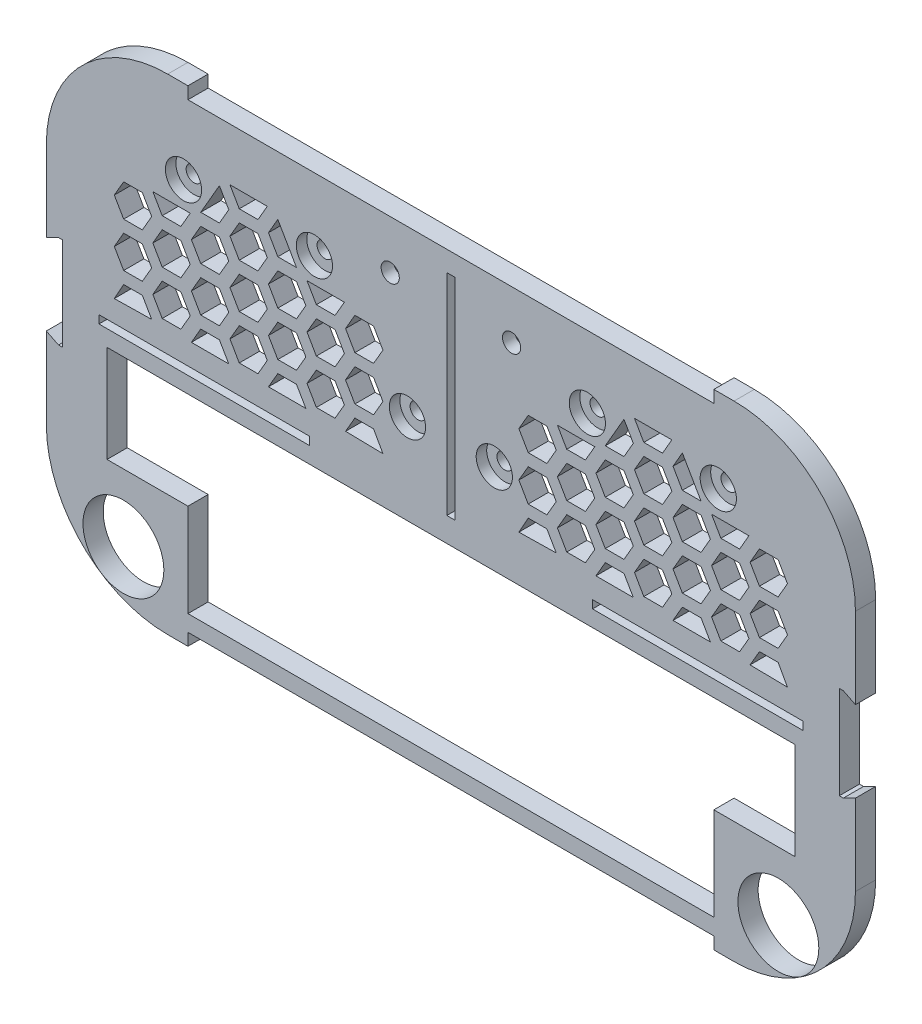
SolidWorks part; units mm, degrees
ref_plane "前视基准面" through (0, 0, 0) normal (0, 0, 1) x (1, 0, 0)
ref_plane "上视基准面" through (0, 0, 0) normal (0, 1, 0) x (1, 0, 0)
ref_plane "右视基准面" through (0, 0, 0) normal (1, 0, 0) x (0, 0, -1)
sketch "草图1" plane through (0, 0, 0) normal (0, 0, 1) x (1, 0, 0)
  line L1 (70, 60) -> (-70, 60)
  line L2 (-100, 30) -> (-100, -30)
  line L4 (70, -60) -> (-70, -60)
  line L5 (100, 30) -> (100, -30)
  arc A0 (-70, 60) -> (-100, 30) centre (-70, 30) ccw
  arc A1 (-70, -60) -> (-100, -30) centre (-70, -30) cw
  arc A2 (70, -60) -> (100, -30) centre (70, -30) ccw
  arc A3 (70, 60) -> (100, 30) centre (70, 30) cw
  point P12 (0, -60)
extrude "凸台-拉伸1" add sketch "草图1" along normal blind 5
sketch "草图2" plane through (0, 0, 0) normal (0, 0, 1) x (1, 0, 0)
  circle A0 centre (-80.95, 46.6721) radius 10
  circle A1 centre (80.95, 46.6721) radius 10
  circle A2 centre (80.95, -46.6721) radius 10
  circle A3 centre (-80.95, -46.6721) radius 10
  point P3 (0, 0)
  point P4 (0, 0)
extrude "孔" cut sketch "草图2" along normal blind 4 contours A1 | A0 region at (-80.95, 46.6721, 0) region at (80.95, 46.6721, 0)
extrude "穿孔" cut sketch "草图2<3>" along normal up to next contours A2 | A3 region at (80.95, -46.6721, 0) region at (-80.95, -46.6721, 0)
sketch "草图2<3>" plane through (0, 0, 0) normal (0, 0, 1) x (1, 0, 0) same geometry as "草图2"
sketch "草图3" plane through (0, 0, 0) normal (0, 0, 1) x (1, 0, 0)
  line L8 (-85, -6) -> (-85, -30)
  line L12 (-70, -30) -> (-65, -30)
  line L22 (-85, -30) -> (-70, -30)
  line L26 (85, -30) -> (70, -30)
  line L32 (70, -30) -> (65, -30)
  line L37 (-65, -30) -> (-65, -53)
  line L39 (65, -53) -> (65, -30)
  line L40 (-65, -60) -> (-65, -57)
  line L41 (-70, -60) -> (70, -60) construction
  line L42 (-65, -57) -> (65, -57)
  line L43 (65, -57) -> (65, -60)
  line L44 (-65, -60) -> (65, -60)
  line L50 (-100, -10) -> (-97, -11.5)
  line L53 (-100, 10) -> (-100, -10)
  line L55 (-85, -6) -> (85, -6)
  line L56 (85, -6) -> (85, -30)
  line L88 (65, -53) -> (-65, -53)
  line L89 (87, 0) -> (87, -2)
  line L90 (87, -2) -> (35, -2)
  line L92 (87, 0) -> (37, 0)
  line L96 (35, 0) -> (35, -2)
  line L105 (-35, 0) -> (-35, -2)
  line L109 (-87, 0) -> (-37, 0)
  line L110 (-87, -2) -> (-35, -2)
  line L111 (-87, 0) -> (-87, -2)
  line L112 (97, 11.5) -> (96, 11.5)
  line L114 (-97, 11.5) -> (-100, 10)
  line L115 (97, 11.5) -> (100, 10)
  line L118 (100, 10) -> (100, -10)
  line L119 (100, -10) -> (97, -11.5)
  line L120 (96, 11.5) -> (96, -11.5)
  line L121 (96, -11.5) -> (97, -11.5)
  line L122 (-97, 11.5) -> (-96, 11.5)
  line L123 (-96, 11.5) -> (-96, -11.5)
  line L124 (-96, -11.5) -> (-97, -11.5)
  line L125 (0, 0) -> (-1, 0)
  line L126 (-1, 0) -> (-1, 50)
  line L128 (1, 50) -> (1, 0)
  line L129 (1, 0) -> (0, 0)
  line L130 (-1, 50) -> (-1, 52)
  line L131 (-1, 52) -> (1, 52)
  line L132 (1, 52) -> (1, 50)
  line L133 (-37, 0) -> (-35, 0)
  line L134 (35, 0) -> (37, 0)
  line L135 (-65, 57) -> (-65, 60)
  line L136 (-65, 57) -> (65, 57)
  line L138 (65, 57) -> (65, 60)
  line L139 (65, 60) -> (-65, 60)
extrude "切除-拉伸4" cut sketch "草图3" along normal up to next
hole_wizard "M3.5 六角头机械螺钉的柱形沉头孔1" positions "3D草图1" profile "草图4" counterbore size "M3.5" standard "ANSI Metric" end condition through all
sketch3d "3D草图1"
  point P31 (-66.0951, 39.3344, 5)
  point P33 (-33.736, 39.2649, 5)
  point P35 (-10.7334, 16.264, 5)
  point P78 (33.736, 39.2649, 5)
  point P80 (10.7334, 16.264, 5)
  point P82 (66.0951, 39.3344, 5)
sketch "草图4" plane through (-66.0951, 39.3344, 5) normal (1, 0, 0) x (0, -1, 0)
  line L0 (0, 0) -> (0, 5)
  line L1 (0, 5) -> (1.95, 5)
  line L3 (1.95, 5) -> (1.95, 2.6)
  line L4 (1.95, 2.6) -> (4.48, 2.6)
  line L5 (4.48, 2.6) -> (4.48, 0)
  line L7 (4.48, 0) -> (0, 0)
  line L11 (0, -6.35) -> (0, 107.95) construction
  dimension "通孔孔直径" = 3.9
  dimension "通孔孔深度" = 5
  dimension "柱形沉头孔直径" = 8.96
  dimension "柱形沉头孔深度" = 2.6
sketch "草图5" plane through (0, 0, 0) normal (0, 0, 1) x (1, 0, 0)
  line L4 (-35.8549, 5.5) -> (-38.1643, 9.5)
  line L6 (-38.1643, 9.5) -> (-42.7831, 9.5)
  line L13 (-42.7831, 9.5) -> (-45.0925, 5.5)
  line L17 (-26.3286, 11) -> (-28.638, 15)
  line L18 (-28.638, 15) -> (-33.2568, 15)
  line L19 (-33.2568, 15) -> (-35.5662, 11)
  line L20 (-35.5662, 11) -> (-33.2568, 7)
  line L21 (-33.2568, 7) -> (-28.638, 7)
  line L22 (-28.638, 7) -> (-26.3286, 11)
  line L23 (-16.8024, 16.5) -> (-19.1118, 20.5)
  line L24 (-19.1118, 20.5) -> (-23.7306, 20.5)
  line L25 (-23.7306, 20.5) -> (-26.04, 16.5)
  line L26 (-26.04, 16.5) -> (-23.7306, 12.5)
  line L27 (-23.7306, 12.5) -> (-19.1118, 12.5)
  line L28 (-19.1118, 12.5) -> (-16.8024, 16.5)
  line L29 (-35.8549, 16.5) -> (-38.1643, 20.5)
  line L30 (-38.1643, 20.5) -> (-42.7831, 20.5)
  line L31 (-42.7831, 20.5) -> (-45.0925, 16.5)
  line L32 (-45.0925, 16.5) -> (-42.7831, 12.5)
  line L33 (-42.7831, 12.5) -> (-38.1643, 12.5)
  line L34 (-38.1643, 12.5) -> (-35.8549, 16.5)
  line L35 (-26.3286, 22) -> (-28.638, 26)
  line L36 (-28.638, 26) -> (-33.2568, 26)
  line L37 (-33.2568, 26) -> (-35.5662, 22)
  line L38 (-35.5662, 22) -> (-33.2568, 18)
  line L39 (-33.2568, 18) -> (-28.638, 18)
  line L40 (-28.638, 18) -> (-26.3286, 22)
  line L41 (-16.8024, 27.5) -> (-19.1118, 31.5)
  line L42 (-19.1118, 31.5) -> (-23.7306, 31.5)
  line L43 (-23.7306, 31.5) -> (-26.04, 27.5)
  line L44 (-26.04, 27.5) -> (-23.7306, 23.5)
  line L45 (-23.7306, 23.5) -> (-19.1118, 23.5)
  line L46 (-19.1118, 23.5) -> (-16.8024, 27.5)
  line L47 (-35.8549, 27.5) -> (-38.1643, 31.5)
  line L48 (-38.1643, 31.5) -> (-42.7831, 31.5)
  line L49 (-42.7831, 31.5) -> (-45.0925, 27.5)
  line L50 (-45.0925, 27.5) -> (-42.7831, 23.5)
  line L51 (-42.7831, 23.5) -> (-38.1643, 23.5)
  line L52 (-38.1643, 23.5) -> (-35.8549, 27.5)
  line L56 (-35.5662, 33) -> (-33.2568, 29)
  line L57 (-33.2568, 29) -> (-28.638, 29)
  line L58 (-28.638, 29) -> (-26.3286, 33)
  line L67 (-42.7831, 42.5) -> (-45.0925, 38.5)
  line L68 (-45.0925, 38.5) -> (-42.7831, 34.5)
  line L69 (-42.7831, 34.5) -> (-38.1643, 34.5)
  line L83 (-45.3812, 11) -> (-47.6906, 15)
  line L84 (-47.6906, 15) -> (-52.3094, 15)
  line L85 (-52.3094, 15) -> (-54.6188, 11)
  line L86 (-54.6188, 11) -> (-52.3094, 7)
  line L87 (-52.3094, 7) -> (-47.6906, 7)
  line L88 (-47.6906, 7) -> (-45.3812, 11)
  line L89 (-45.3812, 22) -> (-47.6906, 26)
  line L90 (-47.6906, 26) -> (-52.3094, 26)
  line L91 (-52.3094, 26) -> (-54.6188, 22)
  line L92 (-54.6188, 22) -> (-52.3094, 18)
  line L93 (-52.3094, 18) -> (-47.6906, 18)
  line L94 (-47.6906, 18) -> (-45.3812, 22)
  line L95 (-45.3812, 33) -> (-47.6906, 37)
  line L96 (-47.6906, 37) -> (-52.3094, 37)
  line L97 (-52.3094, 37) -> (-54.6188, 33)
  line L98 (-54.6188, 33) -> (-52.3094, 29)
  line L99 (-52.3094, 29) -> (-47.6906, 29)
  line L100 (-47.6906, 29) -> (-45.3812, 33)
  line L125 (-42.7831, 42.5) -> (-38.1643, 34.5)
  line L126 (-35.5662, 33) -> (-26.3286, 33)
  line L127 (-45.0925, 5.5) -> (-35.8549, 5.5)
  line L129 (-54.9075, 5.5) -> (-64.1451, 5.5)
  line L130 (-64.4338, 33) -> (-73.6714, 33)
  line L131 (-57.2169, 42.5) -> (-61.8357, 34.5)
  line L132 (-57.2169, 34.5) -> (-61.8357, 34.5)
  line L133 (-54.9075, 38.5) -> (-57.2169, 34.5)
  line L134 (-57.2169, 42.5) -> (-54.9075, 38.5)
  line L135 (-71.362, 29) -> (-73.6714, 33)
  line L136 (-66.7432, 29) -> (-71.362, 29)
  line L137 (-64.4338, 33) -> (-66.7432, 29)
  line L138 (-61.8357, 23.5) -> (-64.1451, 27.5)
  line L139 (-57.2169, 23.5) -> (-61.8357, 23.5)
  line L140 (-54.9075, 27.5) -> (-57.2169, 23.5)
  line L141 (-57.2169, 31.5) -> (-54.9075, 27.5)
  line L142 (-61.8357, 31.5) -> (-57.2169, 31.5)
  line L143 (-64.1451, 27.5) -> (-61.8357, 31.5)
  line L144 (-80.8882, 23.5) -> (-83.1976, 27.5)
  line L145 (-76.2694, 23.5) -> (-80.8882, 23.5)
  line L146 (-73.96, 27.5) -> (-76.2694, 23.5)
  line L147 (-76.2694, 31.5) -> (-73.96, 27.5)
  line L148 (-80.8882, 31.5) -> (-76.2694, 31.5)
  line L149 (-83.1976, 27.5) -> (-80.8882, 31.5)
  line L150 (-71.362, 18) -> (-73.6714, 22)
  line L151 (-66.7432, 18) -> (-71.362, 18)
  line L152 (-64.4338, 22) -> (-66.7432, 18)
  line L153 (-66.7432, 26) -> (-64.4338, 22)
  line L154 (-71.362, 26) -> (-66.7432, 26)
  line L155 (-73.6714, 22) -> (-71.362, 26)
  line L156 (-61.8357, 12.5) -> (-64.1451, 16.5)
  line L157 (-57.2169, 12.5) -> (-61.8357, 12.5)
  line L158 (-54.9075, 16.5) -> (-57.2169, 12.5)
  line L159 (-57.2169, 20.5) -> (-54.9075, 16.5)
  line L160 (-61.8357, 20.5) -> (-57.2169, 20.5)
  line L161 (-64.1451, 16.5) -> (-61.8357, 20.5)
  line L162 (-80.8882, 12.5) -> (-83.1976, 16.5)
  line L163 (-76.2694, 12.5) -> (-80.8882, 12.5)
  line L164 (-73.96, 16.5) -> (-76.2694, 12.5)
  line L165 (-76.2694, 20.5) -> (-73.96, 16.5)
  line L166 (-80.8882, 20.5) -> (-76.2694, 20.5)
  line L167 (-83.1976, 16.5) -> (-80.8882, 20.5)
  line L168 (-71.362, 7) -> (-73.6714, 11)
  line L169 (-66.7432, 7) -> (-71.362, 7)
  line L170 (-64.4338, 11) -> (-66.7432, 7)
  line L171 (-66.7432, 15) -> (-64.4338, 11)
  line L172 (-71.362, 15) -> (-66.7432, 15)
  line L173 (-73.6714, 11) -> (-71.362, 15)
  line L174 (-57.2169, 9.5) -> (-54.9075, 5.5)
  line L175 (-61.8357, 9.5) -> (-57.2169, 9.5)
  line L176 (-64.1451, 5.5) -> (-61.8357, 9.5)
  line L181 (-52.3094, 40) -> (-47.6906, 40)
  line L184 (-52.3094, 44) -> (-54.6188, 44)
  line L185 (-54.6188, 44) -> (-52.3094, 40)
  line L186 (-52.3094, 44) -> (-45.3812, 44)
  line L187 (-45.3812, 44) -> (-47.6906, 40)
  line L188 (-21.4212, 9.5) -> (-23.7306, 9.5)
  line L191 (-26.04, 5.5) -> (-23.7306, 9.5)
  line L192 (-26.04, 5.5) -> (-16.8024, 5.3417)
  line L193 (-16.8024, 5.3417) -> (-19.1118, 9.5)
  line L194 (-19.1118, 9.5) -> (-21.4212, 9.5)
  line L195 (-80.8882, 9.5) -> (-78.5788, 9.5)
  line L196 (-83.1976, 5.3417) -> (-80.8882, 9.5)
  line L197 (-73.96, 5.5) -> (-83.1976, 5.3417)
  line L198 (-73.96, 5.5) -> (-76.2694, 9.5)
  line L199 (-78.5788, 9.5) -> (-76.2694, 9.5)
  line L200 (78.5788, 9.5) -> (76.2694, 9.5)
  line L201 (73.96, 5.5) -> (76.2694, 9.5)
  line L202 (73.96, 5.5) -> (83.1976, 5.3417)
  line L203 (83.1976, 5.3417) -> (80.8882, 9.5)
  line L204 (80.8882, 9.5) -> (78.5788, 9.5)
  line L205 (19.1118, 9.5) -> (21.4212, 9.5)
  line L206 (16.8024, 5.3417) -> (19.1118, 9.5)
  line L207 (26.04, 5.5) -> (16.8024, 5.3417)
  line L208 (26.04, 5.5) -> (23.7306, 9.5)
  line L209 (21.4212, 9.5) -> (23.7306, 9.5)
  line L210 (45.3812, 44) -> (47.6906, 40)
  line L211 (52.3094, 44) -> (45.3812, 44)
  line L212 (54.6188, 44) -> (52.3094, 40)
  line L213 (52.3094, 44) -> (54.6188, 44)
  line L214 (52.3094, 40) -> (47.6906, 40)
  line L215 (64.1451, 5.5) -> (61.8357, 9.5)
  line L216 (61.8357, 9.5) -> (57.2169, 9.5)
  line L217 (57.2169, 9.5) -> (54.9075, 5.5)
  line L218 (73.6714, 11) -> (71.362, 15)
  line L219 (71.362, 15) -> (66.7432, 15)
  line L220 (66.7432, 15) -> (64.4338, 11)
  line L221 (64.4338, 11) -> (66.7432, 7)
  line L222 (66.7432, 7) -> (71.362, 7)
  line L223 (71.362, 7) -> (73.6714, 11)
  line L224 (83.1976, 16.5) -> (80.8882, 20.5)
  line L225 (80.8882, 20.5) -> (76.2694, 20.5)
  line L226 (76.2694, 20.5) -> (73.96, 16.5)
  line L227 (73.96, 16.5) -> (76.2694, 12.5)
  line L228 (76.2694, 12.5) -> (80.8882, 12.5)
  line L229 (80.8882, 12.5) -> (83.1976, 16.5)
  line L230 (64.1451, 16.5) -> (61.8357, 20.5)
  line L231 (61.8357, 20.5) -> (57.2169, 20.5)
  line L232 (57.2169, 20.5) -> (54.9075, 16.5)
  line L233 (54.9075, 16.5) -> (57.2169, 12.5)
  line L234 (57.2169, 12.5) -> (61.8357, 12.5)
  line L235 (61.8357, 12.5) -> (64.1451, 16.5)
  line L236 (73.6714, 22) -> (71.362, 26)
  line L237 (71.362, 26) -> (66.7432, 26)
  line L238 (66.7432, 26) -> (64.4338, 22)
  line L239 (64.4338, 22) -> (66.7432, 18)
  line L240 (66.7432, 18) -> (71.362, 18)
  line L241 (71.362, 18) -> (73.6714, 22)
  line L242 (83.1976, 27.5) -> (80.8882, 31.5)
  line L243 (80.8882, 31.5) -> (76.2694, 31.5)
  line L244 (76.2694, 31.5) -> (73.96, 27.5)
  line L245 (73.96, 27.5) -> (76.2694, 23.5)
  line L246 (76.2694, 23.5) -> (80.8882, 23.5)
  line L247 (80.8882, 23.5) -> (83.1976, 27.5)
  line L248 (64.1451, 27.5) -> (61.8357, 31.5)
  line L249 (61.8357, 31.5) -> (57.2169, 31.5)
  line L250 (57.2169, 31.5) -> (54.9075, 27.5)
  line L251 (54.9075, 27.5) -> (57.2169, 23.5)
  line L252 (57.2169, 23.5) -> (61.8357, 23.5)
  line L253 (61.8357, 23.5) -> (64.1451, 27.5)
  line L254 (64.4338, 33) -> (66.7432, 29)
  line L255 (66.7432, 29) -> (71.362, 29)
  line L256 (71.362, 29) -> (73.6714, 33)
  line L257 (57.2169, 42.5) -> (54.9075, 38.5)
  line L258 (54.9075, 38.5) -> (57.2169, 34.5)
  line L259 (57.2169, 34.5) -> (61.8357, 34.5)
  line L260 (57.2169, 42.5) -> (61.8357, 34.5)
  line L261 (64.4338, 33) -> (73.6714, 33)
  line L262 (54.9075, 5.5) -> (64.1451, 5.5)
  line L263 (45.0925, 5.5) -> (35.8549, 5.5)
  line L264 (35.5662, 33) -> (26.3286, 33)
  line L265 (42.7831, 42.5) -> (38.1643, 34.5)
  line L266 (47.6906, 29) -> (45.3812, 33)
  line L267 (52.3094, 29) -> (47.6906, 29)
  line L268 (54.6188, 33) -> (52.3094, 29)
  line L269 (52.3094, 37) -> (54.6188, 33)
  line L270 (47.6906, 37) -> (52.3094, 37)
  line L271 (45.3812, 33) -> (47.6906, 37)
  line L272 (47.6906, 18) -> (45.3812, 22)
  line L273 (52.3094, 18) -> (47.6906, 18)
  line L274 (54.6188, 22) -> (52.3094, 18)
  line L275 (52.3094, 26) -> (54.6188, 22)
  line L276 (47.6906, 26) -> (52.3094, 26)
  line L277 (45.3812, 22) -> (47.6906, 26)
  line L278 (47.6906, 7) -> (45.3812, 11)
  line L279 (52.3094, 7) -> (47.6906, 7)
  line L280 (54.6188, 11) -> (52.3094, 7)
  line L281 (52.3094, 15) -> (54.6188, 11)
  line L282 (47.6906, 15) -> (52.3094, 15)
  line L283 (45.3812, 11) -> (47.6906, 15)
  line L284 (42.7831, 34.5) -> (38.1643, 34.5)
  line L285 (45.0925, 38.5) -> (42.7831, 34.5)
  line L286 (42.7831, 42.5) -> (45.0925, 38.5)
  line L287 (28.638, 29) -> (26.3286, 33)
  line L288 (33.2568, 29) -> (28.638, 29)
  line L289 (35.5662, 33) -> (33.2568, 29)
  line L290 (38.1643, 23.5) -> (35.8549, 27.5)
  line L291 (42.7831, 23.5) -> (38.1643, 23.5)
  line L292 (45.0925, 27.5) -> (42.7831, 23.5)
  line L293 (42.7831, 31.5) -> (45.0925, 27.5)
  line L294 (38.1643, 31.5) -> (42.7831, 31.5)
  line L295 (35.8549, 27.5) -> (38.1643, 31.5)
  line L296 (19.1118, 23.5) -> (16.8024, 27.5)
  line L297 (23.7306, 23.5) -> (19.1118, 23.5)
  line L298 (26.04, 27.5) -> (23.7306, 23.5)
  line L299 (23.7306, 31.5) -> (26.04, 27.5)
  line L300 (19.1118, 31.5) -> (23.7306, 31.5)
  line L301 (16.8024, 27.5) -> (19.1118, 31.5)
  line L302 (28.638, 18) -> (26.3286, 22)
  line L303 (33.2568, 18) -> (28.638, 18)
  line L304 (35.5662, 22) -> (33.2568, 18)
  line L305 (33.2568, 26) -> (35.5662, 22)
  line L306 (28.638, 26) -> (33.2568, 26)
  line L307 (26.3286, 22) -> (28.638, 26)
  line L308 (38.1643, 12.5) -> (35.8549, 16.5)
  line L309 (42.7831, 12.5) -> (38.1643, 12.5)
  line L310 (45.0925, 16.5) -> (42.7831, 12.5)
  line L311 (42.7831, 20.5) -> (45.0925, 16.5)
  line L312 (38.1643, 20.5) -> (42.7831, 20.5)
  line L313 (35.8549, 16.5) -> (38.1643, 20.5)
  line L314 (19.1118, 12.5) -> (16.8024, 16.5)
  line L315 (23.7306, 12.5) -> (19.1118, 12.5)
  line L316 (26.04, 16.5) -> (23.7306, 12.5)
  line L317 (23.7306, 20.5) -> (26.04, 16.5)
  line L318 (19.1118, 20.5) -> (23.7306, 20.5)
  line L319 (16.8024, 16.5) -> (19.1118, 20.5)
  line L320 (28.638, 7) -> (26.3286, 11)
  line L321 (33.2568, 7) -> (28.638, 7)
  line L322 (35.5662, 11) -> (33.2568, 7)
  line L323 (33.2568, 15) -> (35.5662, 11)
  line L324 (28.638, 15) -> (33.2568, 15)
  line L325 (26.3286, 11) -> (28.638, 15)
  line L326 (42.7831, 9.5) -> (45.0925, 5.5)
  line L327 (38.1643, 9.5) -> (42.7831, 9.5)
  line L328 (35.8549, 5.5) -> (38.1643, 9.5)
extrude "切除-拉伸5" cut sketch "草图5" against normal through all and the other way through all
ref_plane "基准面1" through (0, 0, 0) normal (0, 0, -1) x (-1, 0, 0)
sketch "草图8" plane through (0, 0, 0) normal (0, 0, 1) x (1, 0, 0)
  line L0 (-6, 22) -> (-1, 22)
  line L5 (-26, 52) -> (-26, 47)
  line L7 (-24, 47) -> (-24, 52)
  line L8 (-26, 47) -> (-66, 47)
  line L9 (-66, 47) -> (-66, 52)
  line L10 (-66, 52) -> (-26, 52)
  line L18 (-1, 22) -> (-1, 52)
  line L20 (-24, 52) -> (-1, 52)
  line L42 (24, 47) -> (6, 22)
  line L43 (-24, 47) -> (-6, 22)
  line L44 (24, 52) -> (1, 52)
  line L45 (1, 22) -> (1, 52)
  line L46 (66, 52) -> (26, 52)
  line L47 (66, 47) -> (66, 52)
  line L48 (26, 47) -> (66, 47)
  line L49 (24, 47) -> (24, 52)
  line L50 (26, 52) -> (26, 47)
  line L51 (6, 22) -> (1, 22)
  circle A6 centre (15, 45) radius 5
  circle A7 centre (-15, 45) radius 5
extrude "切除-拉伸7" cut sketch "草图8" along normal blind 3
hole_wizard "M4 六角凹头盖的柱孔1" positions "3D草图4" profile "草图11" counterbore size "M4" standard "BSI" end condition through all
sketch3d "3D草图4"
  line L5 (15, 45, 3) -> (-15, 45, 3)
  line L6 (15, 45, 3) -> (15, 45, 0) construction
  line L7 (-15, 45, 3) -> (-15, 45, 0) construction
  point P17 (15, 45, 0)
  point P19 (-15, 45, 0)
sketch "草图11" plane through (-15, 45, 0) normal (1, 0, 0) x (0, 1, 0)
  line L0 (0, 0) -> (0, 5)
  line L1 (0, 5) -> (2.25, 5)
  line L3 (2.25, 5) -> (2.25, 2)
  line L4 (2.25, 2) -> (4, 2)
  line L5 (4, 2) -> (4, 0)
  line L7 (4, 0) -> (0, 0)
  line L11 (0, -6.35) -> (0, 107.95) construction
  dimension "通孔孔直径" = 4.5
  dimension "通孔孔深度" = 5
  dimension "柱形沉头孔直径" = 8
  dimension "柱形沉头孔深度" = 2
